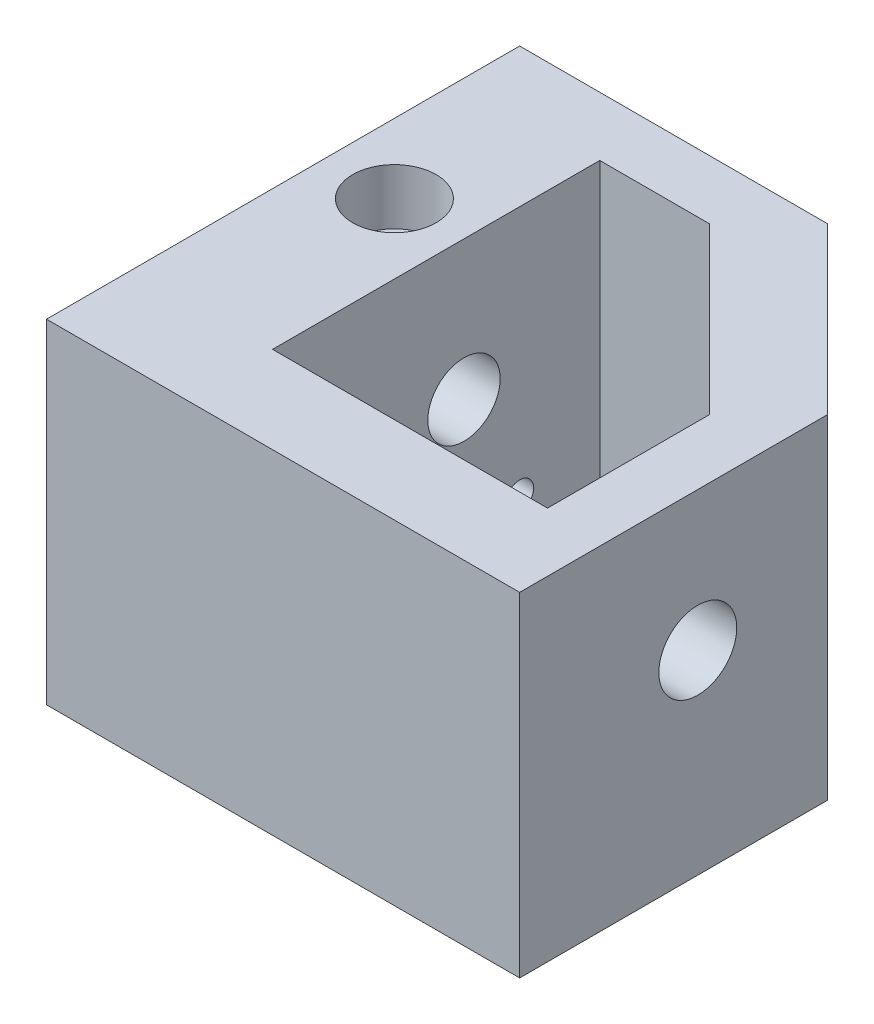
SolidWorks part; units mm, degrees
ref_plane "Front Plane" through (0, 0, 0) normal (0, 0, 1) x (1, 0, 0)
ref_plane "Top Plane" through (0, 0, 0) normal (0, 1, 0) x (1, 0, 0)
ref_plane "Right Plane" through (0, 0, 0) normal (1, 0, 0) x (0, 0, -1)
sketch "Sketch1" plane through (0, 0, 0) normal (0, 1, 0) x (1, 0, 0)
  line L0 (-42.7058, 39.6026) -> (-42.7058, -40.3974)
  line L1 (-42.7058, -40.3974) -> (42.2942, -40.3974)
  line L2 (42.2942, -40.3974) -> (42.2942, 9.9041)
  line L3 (12.5957, 39.6026) -> (42.2942, 9.9041)
  line L4 (-42.7058, 39.6026) -> (12.5957, 39.6026)
  line L5 (-17.7058, 28.9926) -> (-17.7058, -29.7874)
  line L6 (-17.7058, -29.7874) -> (31.691, -29.7874)
  line L7 (31.691, -29.7874) -> (31.691, -0.7059)
  line L8 (-17.7058, 28.9926) -> (1.9925, 28.9926)
  line L9 (1.9925, 28.9926) -> (31.691, -0.7059)
  dimension "D1" = 80
  dimension "D2" = 85
  dimension "D3" = 42
  dimension "D4" = 135
  dimension "D5" = 25
  dimension "D6" = 10.61
  dimension "D7" = 15
  dimension "D8" = 42
  dimension "D9" = 10.61
extrude "Boss-Extrude2" add sketch "Sketch1" along normal blind 60
sketch "Sketch4" plane through (0, 0, 0) normal (0, -1, 0) x (-1, 0, 0)
  line L0 (17.7058, 28.9926) -> (-1.9925, 28.9926)
  line L1 (-1.9925, 28.9926) -> (-31.691, -0.7059)
  line L2 (-31.691, -0.7059) -> (-31.691, -29.7874)
  line L3 (-31.691, -29.7874) -> (17.7058, -29.7874)
  line L4 (17.7058, -29.7874) -> (17.7058, 28.9926)
extrude "Boss-Extrude3" add sketch "Sketch4" against normal blind 10
sketch "Sketch8" plane through (26.0992, 0, -26.0992) normal (0.7071, 0, -0.7071) x (-0.7071, 0, -0.7071)
  line L0 (-22.9032, 60) -> (-22.9032, 0) construction
  line L1 (-20.9032, 54) -> (17.0968, 54) construction
  line L2 (-20.9032, 54) -> (-20.9032, 16) construction
  line L3 (-20.9032, 16) -> (17.0968, 16) construction
  line L4 (17.0968, 54) -> (17.0968, 16) construction
  line L5 (-22.9032, 60) -> (19.0968, 60) construction
  circle A0 centre (11.0968, 48) radius 4.75
  circle A1 centre (11.0968, 34) radius 3
  circle A2 centre (11.0968, 22) radius 4.75
  circle A3 centre (-0.9032, 22) radius 3
  circle A4 centre (-14.9032, 22) radius 4.75
  dimension "D3" = 9.5
  dimension "D5" = 9.5
  dimension "D6" = 6
  dimension "D7" = 9.5
  dimension "D10" = 6
  dimension "D11" = 6
  dimension "D12" = 6
  dimension "D15" = 6
  dimension "D16" = 6
  dimension "D18" = 18
  dimension "D1" = 38
  dimension "D2" = 38
  dimension "D4" = 6
  dimension "D8" = 6
  dimension "D9" = 6
  dimension "D13" = 6
  dimension "D14" = 18
  dimension "D17" = 6
  dimension "D19" = 6
  dimension "D20" = 2
extrude "Cut-Extrude2" cut sketch "Sketch8" against normal up to next
sketch "Sketch9" plane through (-42.7058, 0, 0) normal (-1, 0, 0) x (0, 0, 1)
  line L0 (-39.6026, 60) -> (-39.6026, 0) construction
  line L2 (-39.6026, 60) -> (40.3974, 60) construction
  circle A0 centre (-4.6026, 35) radius 6.5
  dimension "D3" = 13
  dimension "D1" = 35
  dimension "D2" = 25
extrude "Cut-Extrude3" cut sketch "Sketch9" against normal up to next
sketch "Sketch10" plane through (42.2942, 0, 0) normal (1, 0, 0) x (0, 0, -1)
  line L0 (-40.3974, 60) -> (9.9041, 60) construction
  line L1 (-40.3974, 60) -> (-40.3974, 0) construction
  circle A0 centre (-13.3974, 35) radius 7
  dimension "D2" = 27
  dimension "D3" = 14
  dimension "D1" = 25
extrude "Cut-Extrude4" cut sketch "Sketch10" against normal up to next
sketch "Sketch12" plane through (0, 60, 0) normal (0, 1, 0) x (1, 0, 0)
  line L0 (12.5957, 39.6026) -> (-42.7058, 39.6026) construction
  line L2 (-42.7058, 39.6026) -> (-42.7058, -40.3974) construction
  circle A0 centre (-30.2058, 4.6026) radius 7.5
  dimension "D2" = 12.5
  dimension "D3" = 15
  dimension "D1" = 35
extrude "Cut-Extrude6" cut sketch "Sketch12" against normal blind 10
sketch "Sketch24" plane through (0, 50, 0) normal (0, 1, 0) x (1, 0, 0)
  line L0 (-30.2058, 4.6026) -> (-22.7058, 4.6026) construction
  line L1 (-30.2058, 4.6026) -> (-37.7058, 4.6026) construction
  circle A0 centre (-30.2058, 4.6026) radius 7.5 construction
  circle A1 centre (-26.4558, 4.6026) radius 2.25
  circle A2 centre (-33.9558, 4.6026) radius 2.25
  dimension "D1" = 4.5
  dimension "D2" = 4.5
extrude "Cut-Extrude16" cut sketch "Sketch24" against normal up to next
sketch "Sketch33" plane through (-42.7058, 0, 0) normal (-1, 0, 0) x (0, 0, 1)
  circle A0 centre (5.3974, 38) radius 1.5
  circle A1 centre (-4.6026, 35) radius 6.5 construction
  circle A2 centre (5.3974, 32) radius 1.5
  dimension "D1" = 3
  dimension "D2" = 10
  dimension "D3" = 3
  dimension "D5" = 10
  dimension "D6" = 3
  dimension "D4" = 6
extrude "Cut-Extrude18" cut sketch "Sketch33" against normal blind 10
sketch "Sketch37" plane through (0, 0, 40.3974) normal (0, 0, 1) x (1, 0, 0)
  line L1 (42.2942, 60) -> (-42.7058, 60)
  line L2 (42.2942, 60) -> (42.2942, 0)
  line L3 (42.2942, 0) -> (-42.7058, 0)
  line L4 (-42.7058, 60) -> (-42.7058, 0)
extrude "Boss-Extrude7" add sketch "Sketch37" along normal blind 5
sketch "Sketch38" plane through (-42.7058, 0, 0) normal (-1, 0, 0) x (0, 0, 1)
  line L0 (-39.6026, 0) -> (45.3974, 0) construction
  line L1 (-39.6026, 60) -> (-39.6026, 0) construction
  line L2 (45.3974, 60) -> (45.3974, 0) construction
  line L3 (-39.6026, 60) -> (45.3974, 60) construction
  circle A0 centre (-19.6026, 5) radius 2.5
  circle A1 centre (25.3974, 5) radius 2.5
  circle A2 centre (-36.8526, 40) radius 2
  circle A3 centre (42.6474, 40) radius 2
  dimension "D1" = 4
  dimension "D2" = 5
  dimension "D3" = 5
  dimension "D4" = 4
  dimension "D5" = 5
  dimension "D6" = 5
  dimension "D7" = 2.75
  dimension "D8" = 2.75
  dimension "D9" = 20
  dimension "D10" = 20
  dimension "D11" = 20
  dimension "D12" = 20
extrude "Cut-Extrude19" cut sketch "Sketch38" against normal blind 20
sketch "Sketch39" plane through (-42.7058, 0, 0) normal (-1, 0, 0) x (0, 0, 1)
  line L0 (-39.6026, 0) -> (45.3974, 0) construction
  line L1 (-39.6026, 60) -> (-39.6026, 0) construction
  circle A0 centre (-14.6026, 15) radius 2.5
  dimension "D1" = 5
  dimension "D2" = 15
  dimension "D3" = 25
extrude "Cut-Extrude20" cut sketch "Sketch39" against normal up to next
sketch "Sketch40" plane through (0, 0, 0) normal (0, -1, 0) x (1, 0, 0)
  line L0 (12.5957, -39.6026) -> (-42.7058, -39.6026) construction
  line L1 (-42.7058, -39.6026) -> (-42.7058, 45.3974) construction
  line L2 (-42.7058, 45.3974) -> (42.2942, 45.3974) construction
  line L3 (42.2942, 45.3974) -> (42.2942, -9.9041) construction
  line L4 (42.2942, -9.9041) -> (12.5957, -39.6026) construction
  circle A0 centre (-36.7058, -33.6026) radius 2
  circle A1 centre (-36.7058, 39.3974) radius 2
  circle A2 centre (36.2942, 39.3974) radius 2
  circle A3 centre (36.2942, -7.4189) radius 2
  circle A4 centre (10.1104, -33.6026) radius 2
  dimension "D1" = 4
  dimension "D2" = 4
  dimension "D3" = 4
  dimension "D4" = 4
  dimension "D5" = 4
  dimension "D6" = 6
  dimension "D7" = 6
  dimension "D8" = 6
  dimension "D9" = 6
  dimension "D10" = 6
  dimension "D11" = 6
  dimension "D12" = 6
  dimension "D13" = 6
  dimension "D14" = 6
  dimension "D15" = 6
extrude "Cut-Extrude21" cut sketch "Sketch40" against normal blind 10
sketch "Sketch41" plane through (26.0992, 0, -26.0992) normal (0.7071, 0, -0.7071) x (-0.7071, 0, -0.7071)
  circle A0 centre (14.0968, 34) radius 1.15
  circle A1 centre (11.0968, 34) radius 3 construction
  circle A2 centre (8.0968, 34) radius 1.15
  circle A3 centre (-0.9032, 25) radius 1.15
  circle A4 centre (-0.9032, 22) radius 3 construction
  circle A5 centre (-0.9032, 19) radius 1.15
  dimension "D1" = 2.3
  dimension "D2" = 2.3
  dimension "D3" = 2.3
  dimension "D4" = 2.3
extrude "Cut-Extrude22" cut sketch "Sketch41" against normal blind 2.5
